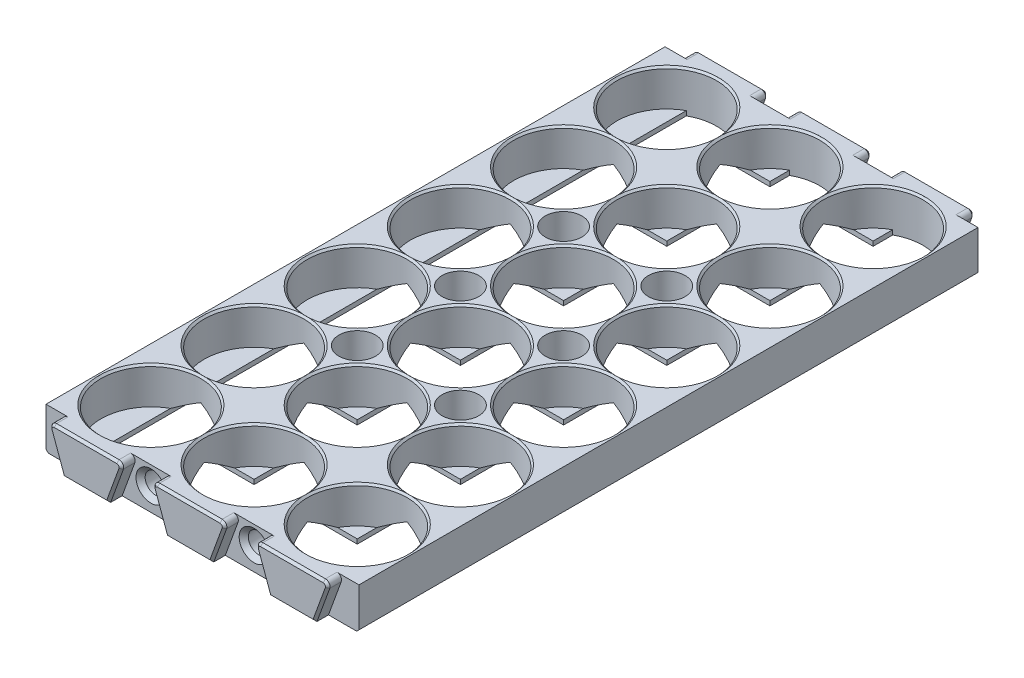
SolidWorks part; units mm, degrees
ref_plane "Front Plane" through (0, 0, 0) normal (0, 0, 1) x (1, 0, 0)
ref_plane "Top Plane" through (0, 0, 0) normal (0, 1, 0) x (1, 0, 0)
ref_plane "Right Plane" through (0, 0, 0) normal (1, 0, 0) x (0, 0, -1)
sketch "Sketch1" plane through (0, 0, 0) normal (0, 1, 0) x (1, 0, 0)
  line L0 (-11.25, 10.875) -> (11.25, 10.875) construction
  line L1 (-11.25, -11.25) -> (11.25, -11.25)
  line L2 (-11.25, -11.25) -> (-11.25, 11.25)
  line L3 (-11.25, 11.25) -> (11.25, 11.25)
  line L4 (11.25, -11.25) -> (11.25, 11.25)
  line L5 (-11.25, -11.25) -> (11.25, 11.25) construction
  line L6 (-11.25, 11.25) -> (11.25, -11.25) construction
  circle A0 centre (0, 0) radius 10.875
  point P0 (0, 0)
  dimension "D1" = 21.75
  dimension "D2" = 22.5
  dimension "D3" = 0.375
extrude "Boss-Extrude1" add sketch "Sketch1" along normal blind 8
sketch "Sketch2" plane through (0, 0, 0) normal (0, -1, 0) x (1, 0, 0)
  line L0 (5.25, 11.25) -> (-5.25, 11.25) construction
  line L1 (11.25, 11.25) -> (5.25, 11.25)
  line L2 (11.25, 11.25) -> (11.25, 5.25)
  line L3 (11.25, 5.25) -> (5.25, 5.25)
  line L4 (5.25, 11.25) -> (5.25, 5.25)
  line L5 (11.25, -11.25) -> (5.25, -11.25)
  line L6 (11.25, -11.25) -> (11.25, -5.25)
  line L7 (11.25, -5.25) -> (5.25, -5.25)
  line L8 (5.25, -11.25) -> (5.25, -5.25)
  line L9 (-11.25, -11.25) -> (-5.25, -11.25)
  line L10 (-11.25, -11.25) -> (-11.25, -5.25)
  line L11 (-11.25, -5.25) -> (-5.25, -5.25)
  line L12 (-5.25, -11.25) -> (-5.25, -5.25)
  line L13 (-11.25, 11.25) -> (-5.25, 11.25)
  line L14 (-11.25, 11.25) -> (-11.25, 5.25)
  line L15 (-11.25, 5.25) -> (-5.25, 5.25)
  line L16 (-5.25, 11.25) -> (-5.25, 5.25)
  line L17 (11.25, 5.25) -> (11.25, -5.25) construction
  line L18 (5.25, -11.25) -> (-5.25, -11.25) construction
  line L19 (-11.25, 5.25) -> (-11.25, -5.25) construction
  dimension "D1" = 10.5
extrude "Boss-Extrude2" add sketch "Sketch2" along normal blind 1
chamfer "Chamfer2" distance 0.4 angle 45 1 edges at (0, 8, 10.875)
pattern_linear "LPattern1" count 6 spacing 22.5 along (0, 0, 1) count 3 spacing 22.5 along (1, 0, 0) of "Boss-Extrude2", "Boss-Extrude1", "Chamfer2"
sketch "Sketch5" plane through (0, 0, -5.25) normal (0, 0, 1) x (1, 0, 0)
  line L25 (-5.25, -1) -> (-5.25, 0) construction
  line L26 (-5.25, -1) -> (-11.25, -1) construction
  line L27 (-11.25, -1) -> (-11.25, 0) construction
  line L29 (-5.25, 0) -> (-9.5238, 0) construction
  line L35 (-5.25, -1) -> (-5.25, 0)
  line L36 (-5.25, -1) -> (-11.25, -1)
  line L37 (-11.25, -1) -> (-11.25, 0)
  line L39 (-5.25, 0) -> (-11.25, 0)
  line L55 (56.25, -1) -> (50.25, -1)
  line L56 (56.25, -1) -> (56.25, 0)
  line L57 (56.25, 0) -> (50.25, 0)
  line L58 (50.25, -1) -> (50.25, 0)
  dimension "D1" = 6
extrude "Boss-Extrude3" add sketch "Sketch5" along normal up to surface (129 mm away)
sketch "Sketch6" plane through (0, 0, 0) normal (0, -1, 0) x (1, 0, 0)
  line L27 (39.75, -11.25) -> (50.25, -11.25) construction
  line L28 (50.25, -11.25) -> (50.25, -9.5238) construction
  line L29 (39.75, -9.5238) -> (39.75, -11.25) construction
  line L30 (17.25, -9.5238) -> (17.25, -11.25) construction
  line L31 (17.25, -11.25) -> (27.75, -11.25) construction
  line L32 (27.75, -11.25) -> (27.75, -9.5238) construction
  line L33 (-5.25, -9.5238) -> (-5.25, -11.25) construction
  line L34 (-5.25, -11.25) -> (5.25, -11.25) construction
  line L35 (5.25, -11.25) -> (5.25, -9.5238) construction
  line L51 (39.75, -11.25) -> (50.25, -11.25)
  line L52 (50.25, -11.25) -> (50.25, -9.5238)
  line L53 (39.75, -9.5238) -> (39.75, -11.25)
  line L54 (17.25, -9.5238) -> (17.25, -11.25)
  line L55 (17.25, -11.25) -> (27.75, -11.25)
  line L56 (27.75, -11.25) -> (27.75, -9.5238)
  line L57 (-5.25, -9.5238) -> (-5.25, -11.25)
  line L58 (-5.25, -11.25) -> (5.25, -11.25)
  line L59 (5.25, -11.25) -> (5.25, -9.5238)
  line L63 (50.25, 122.0238) -> (50.25, 123.75) construction
  line L64 (50.25, 123.75) -> (39.75, 123.75) construction
  line L65 (39.75, 123.75) -> (39.75, 122.0238) construction
  line L66 (27.75, 122.0238) -> (27.75, 123.75) construction
  line L67 (27.75, 123.75) -> (17.25, 123.75) construction
  line L68 (17.25, 123.75) -> (17.25, 122.0238) construction
  line L69 (5.25, 123.75) -> (-5.25, 123.75) construction
  line L70 (-5.25, 123.75) -> (-5.25, 122.0238) construction
  line L71 (5.25, 122.0238) -> (5.25, 123.75) construction
  line L75 (50.25, 122.0238) -> (50.25, 123.75)
  line L76 (50.25, 123.75) -> (39.75, 123.75)
  line L77 (39.75, 123.75) -> (39.75, 122.0238)
  line L78 (27.75, 122.0238) -> (27.75, 123.75)
  line L79 (27.75, 123.75) -> (17.25, 123.75)
  line L80 (17.25, 123.75) -> (17.25, 122.0238)
  line L81 (5.25, 123.75) -> (-5.25, 123.75)
  line L82 (-5.25, 123.75) -> (-5.25, 122.0238)
  line L83 (5.25, 122.0238) -> (5.25, 123.75)
  arc A9 (39.75, -9.5238) -> (50.25, -9.5238) centre (45, 0) ccw construction
  arc A10 (17.25, -9.5238) -> (27.75, -9.5238) centre (22.5, 0) ccw construction
  arc A11 (-5.25, -9.5238) -> (5.25, -9.5238) centre (0, 0) ccw construction
  arc A17 (39.75, -9.5238) -> (50.25, -9.5238) centre (45, 0) ccw
  arc A18 (17.25, -9.5238) -> (27.75, -9.5238) centre (22.5, 0) ccw
  arc A19 (-5.25, -9.5238) -> (5.25, -9.5238) centre (0, 0) ccw
  arc A21 (50.25, 122.0238) -> (39.75, 122.0238) centre (45, 112.5) ccw construction
  arc A22 (27.75, 122.0238) -> (17.25, 122.0238) centre (22.5, 112.5) ccw construction
  arc A23 (5.25, 122.0238) -> (-5.25, 122.0238) centre (0, 112.5) ccw construction
  arc A25 (50.25, 122.0238) -> (39.75, 122.0238) centre (45, 112.5) ccw
  arc A26 (27.75, 122.0238) -> (17.25, 122.0238) centre (22.5, 112.5) ccw
  arc A27 (5.25, 122.0238) -> (-5.25, 122.0238) centre (0, 112.5) ccw
extrude "Boss-Extrude4" add sketch "Sketch6" along normal up to surface (1 mm away) up to face at (-8.25, -1, 56.25)
sketch "Sketch7" plane through (0, 0, 0) normal (0, 0, 1) x (1, 0, 0)
  line L1 (-5.25, 0) -> (5.25, 0)
  line L2 (-5.25, 0) -> (0, 5.25) construction
  line L3 (0, 5.25) -> (5.25, 0) construction
  line L4 (0, 0) -> (0, 7.975) construction
  line L6 (-5.25, 0) -> (0, 3.0311)
  line L7 (0, 3.0311) -> (5.25, 0)
  line L9 (-5.25, -1) -> (-5.25, 0) construction
  line L10 (5.25, -1) -> (5.25, 0) construction
  line L11 (-5.25, -1) -> (-5.25, 0) construction
  line L12 (5.25, -1) -> (5.25, 0) construction
  line L13 (17.25, 0) -> (22.5, 3.0311)
  line L14 (22.5, 3.0311) -> (27.75, 0)
  line L15 (17.25, 0) -> (27.75, 0)
  line L16 (39.75, 0) -> (45, 3.0311)
  line L17 (45, 3.0311) -> (50.25, 0)
  line L18 (39.75, 0) -> (50.25, 0)
  line L22 (-5.25, 0) -> (17.25, 0) construction
  line L23 (62.25, 0) -> (67.5, 3.0311) [skipped]
  line L24 (67.5, 3.0311) -> (72.75, 0) [skipped]
  line L25 (62.25, 0) -> (72.75, 0) [skipped]
  parabola Q0 (0.7504, 8) -> (-0.7504, 8) focus (0, 13.6125) apex (0, 7.975) construction
  dimension "D1" = 45
  dimension "D2" = 30
  dimension "D3" = 4.9439
  dimension "D5" = 22.5
  dimension "D4" = 4
extrude "Cut-Extrude1" cut sketch "Sketch7" along normal up to surface (117.75 mm away) up to face at (11.25, -0.3333, 117.75)
sketch "Sketch16" plane through (0, 0, 0) normal (1, 0, 0) x (0, 0, -1)
  line L2 (-5.25, -1) -> (-5.25, 0) construction
  line L3 (5.25, -1) -> (5.25, 0) construction
  line L4 (-5.25, 0) -> (0, 3.0311)
  line L5 (0, 3.0311) -> (5.25, 0)
  line L6 (-5.25, 0) -> (5.25, 0)
  line L7 (-5.25, -1) -> (-5.25, 0) construction
  line L8 (5.25, -1) -> (5.25, 0) construction
  line L9 (-22.5, 3.0311) -> (-17.25, 0)
  line L10 (-27.75, 0) -> (-17.25, 0)
  line L11 (-27.75, 0) -> (-22.5, 3.0311)
  line L12 (-45, 3.0311) -> (-39.75, 0)
  line L13 (-50.25, 0) -> (-39.75, 0)
  line L14 (-50.25, 0) -> (-45, 3.0311)
  line L15 (-67.5, 3.0311) -> (-62.25, 0)
  line L16 (-72.75, 0) -> (-62.25, 0)
  line L17 (-72.75, 0) -> (-67.5, 3.0311)
  line L18 (-90, 3.0311) -> (-84.75, 0)
  line L19 (-95.25, 0) -> (-84.75, 0)
  line L20 (-95.25, 0) -> (-90, 3.0311)
  line L21 (-112.5, 3.0311) -> (-107.25, 0)
  line L22 (-117.75, 0) -> (-107.25, 0)
  line L23 (-117.75, 0) -> (-112.5, 3.0311)
  line L42 (0, 3.0311) -> (-22.5, 3.0311) construction
  line L43 (-135, 3.0311) -> (-129.75, 0) [skipped]
  line L44 (-140.25, 0) -> (-129.75, 0) [skipped]
  line L45 (-140.25, 0) -> (-135, 3.0311) [skipped]
  line L46 (-157.5, 3.0311) -> (-152.25, 0) [skipped]
  line L47 (-162.75, 0) -> (-152.25, 0) [skipped]
  line L48 (-162.75, 0) -> (-157.5, 3.0311) [skipped]
  line L49 (-180, 3.0311) -> (-174.75, 0) [skipped]
  line L50 (-185.25, 0) -> (-174.75, 0) [skipped]
  line L51 (-185.25, 0) -> (-180, 3.0311) [skipped]
  line L52 (-202.5, 3.0311) -> (-197.25, 0) [skipped]
  line L53 (-207.75, 0) -> (-197.25, 0) [skipped]
  line L54 (-207.75, 0) -> (-202.5, 3.0311) [skipped]
  line L55 (-225, 3.0311) -> (-219.75, 0) [skipped]
  line L56 (-230.25, 0) -> (-219.75, 0) [skipped]
  line L57 (-230.25, 0) -> (-225, 3.0311) [skipped]
  line L58 (-247.5, 3.0311) -> (-242.25, 0) [skipped]
  line L59 (-252.75, 0) -> (-242.25, 0) [skipped]
  line L60 (-252.75, 0) -> (-247.5, 3.0311) [skipped]
  dimension "D1" = 30
  dimension "D3" = 22.5
  dimension "D2" = 12
extrude "Cut-Extrude7" cut sketch "Sketch16" along normal up to surface (39.75 mm away) up to face at (39.75, -0.3333, 11.25)
sketch "Sketch8" plane through (0, 0, -11.25) normal (0, 0, -1) x (-1, 0, 0)
  line L0 (0, -1) -> (0, 8) construction
  line L1 (-27.4743, -1) -> (-30.75, 8)
  line L2 (0.7504, 8) -> (11.25, 8) construction
  line L3 (4.9743, -1) -> (-4.9743, -1)
  line L4 (-4.9743, -1) -> (-8.25, 8)
  line L5 (-8.25, 8) -> (8.25, 8)
  line L6 (4.9743, -1) -> (8.25, 8)
  line L7 (11.25, 8) -> (11.25, -1) construction
  line L8 (11.25, -1) -> (-56.25, -1) construction
  line L9 (-30.75, 8) -> (-14.25, 8)
  line L10 (0.7504, 8) -> (11.25, 8) construction
  line L11 (-17.5257, -1) -> (-14.25, 8)
  line L12 (-17.5257, -1) -> (-27.4743, -1)
  line L13 (-49.9743, -1) -> (-53.25, 8)
  line L14 (-53.25, 8) -> (-36.75, 8)
  line L15 (-40.0257, -1) -> (-36.75, 8)
  line L16 (-40.0257, -1) -> (-49.9743, -1)
  line L21 (-4.9743, -1) -> (-27.4743, -1) construction
  line L22 (0.7504, 8) -> (11.25, 8) construction
  line L23 (-72.4743, -1) -> (-75.75, 8) [skipped]
  line L24 (-75.75, 8) -> (-59.25, 8) [skipped]
  line L25 (-62.5257, -1) -> (-59.25, 8) [skipped]
  line L26 (-62.5257, -1) -> (-72.4743, -1) [skipped]
  dimension "D1" = 70
  dimension "D2" = 3
  dimension "D4" = 22.5
  dimension "D5" = 9
  dimension "D3" = 4
sketch "Sketch9" plane through (0, 0, 123.75) normal (0, 0, 1) x (1, 0, 0)
  line L24 (-4.9743, -1) -> (4.9743, -1)
  line L25 (4.9743, -1) -> (8.25, 8)
  line L26 (8.25, 8) -> (-8.25, 8)
  line L27 (-8.25, 8) -> (-4.9743, -1)
  line L28 (-4.9743, -1) -> (4.9743, -1)
  line L29 (4.9743, -1) -> (8.25, 8)
  line L30 (8.25, 8) -> (-8.25, 8)
  line L31 (-8.25, 8) -> (-4.9743, -1)
  line L40 (49.9743, -1) -> (53.25, 8)
  line L41 (53.25, 8) -> (36.75, 8)
  line L42 (36.75, 8) -> (40.0257, -1)
  line L43 (40.0257, -1) -> (49.9743, -1)
  line L44 (49.9743, -1) -> (53.25, 8)
  line L45 (53.25, 8) -> (36.75, 8)
  line L46 (36.75, 8) -> (40.0257, -1)
  line L47 (40.0257, -1) -> (49.9743, -1)
  line L48 (14.25, 8) -> (17.5257, -1)
  line L49 (17.5257, -1) -> (27.4743, -1)
  line L50 (27.4743, -1) -> (30.75, 8)
  line L51 (30.75, 8) -> (14.25, 8)
  line L52 (14.25, 8) -> (17.5257, -1)
  line L53 (17.5257, -1) -> (27.4743, -1)
  line L54 (27.4743, -1) -> (30.75, 8)
  line L55 (30.75, 8) -> (14.25, 8)
  dimension "D1" = 0
  dimension "D3" = 0
  dimension "D4" = 0
extrude "Boss-Extrude5" add sketch "Sketch8" along normal blind 3
extrude "Boss-Extrude6" add sketch "Sketch9" along normal blind 3
fillet "Fillet1" radius 1 12 edges at (8.25, 8, 125.25) (14.25, 8, 125.25) (30.75, 8, 125.25) (36.75, 8, 125.25) (53.25, 8, 125.25) (-8.25, 8, 125.25) (53.25, 8, -12.75) (30.75, 8, -12.75) (36.75, 8, -12.75) (8.25, 8, -12.75) (14.25, 8, -12.75) (-8.25, 8, -12.75)
chamfer "Chamfer3" distance 0.5 angle 45 36 edges at (6.3679, 2.829, -14.25) (0, 8, -14.25) (-6.3679, 2.829, -14.25) (51.3679, 2.829, -14.25) (45, 8, -14.25) (38.6321, 2.829, -14.25) (28.8679, 2.829, -14.25) (22.5, 8, -14.25) (16.1321, 2.829, -14.25) (51.3679, 2.829, 126.75) (38.6321, 2.829, 126.75) (45, 8, 126.75) (28.8679, 2.829, 126.75) (16.1321, 2.829, 126.75) (22.5, 8, 126.75) (6.3679, 2.829, 126.75) (-6.3679, 2.829, 126.75) (0, 8, 126.75) (45, -1, 126.75) (22.5, -1, 126.75) (0, -1, 126.75) (45, -1, -14.25) (22.5, -1, -14.25) (0, -1, -14.25) (52.641, 7.5736, 126.75) (37.359, 7.5736, 126.75) (30.141, 7.5736, 126.75) (14.859, 7.5736, 126.75) (7.641, 7.5736, 126.75) (-7.641, 7.5736, 126.75) (52.641, 7.5736, -14.25) (37.359, 7.5736, -14.25) (30.141, 7.5736, -14.25) (14.859, 7.5736, -14.25) (7.641, 7.5736, -14.25) (-7.641, 7.5736, -14.25)
sketch "Sketch10" plane through (0, 0, -11.25) normal (0, 0, -1) x (-1, 0, 0)
  line L0 (-11.25, -1) -> (-11.25, 8) construction
  line L1 (-29.3219, 8) -> (-15.6781, 8) construction
  line L2 (-4.9743, -1) -> (-17.5257, -1) construction
  line L3 (-26.9422, -1) -> (-18.0578, -1) construction
  line L4 (-14.25, 8) -> (-8.25, 8) construction
  line L5 (-22.5, 8) -> (-22.5, -1) construction
  circle A0 centre (-11.25, 4) radius 2.25
  circle A1 centre (-33.75, 4) radius 2.25
  dimension "D2" = 4.5
  dimension "D1" = 4
sketch "Sketch11" plane through (0, 0, 123.75) normal (0, 0, 1) x (1, 0, 0)
  circle A0 centre (11.25, 4) radius 2.25 construction
  circle A1 centre (11.25, 4) radius 2.25
  circle A2 centre (33.75, 4) radius 2.25 construction
  circle A3 centre (33.75, 4) radius 2.25
extrude "Cut-Extrude2" cut sketch "Sketch10" against normal blind 5
extrude "Cut-Extrude3" cut sketch "Sketch11" against normal blind 5
chamfer "Chamfer5" distance 1 angle 45 4 edges at (36, 4, -11.25) (9, 4, -11.25) (13.5, 4, 123.75) (36, 4, 123.75)
sketch "Sketch17" plane through (0, -1, 0) normal (0, -1, 0) x (1, 0, 0)
  line L0 (5.25, 5.25) -> (17.25, 17.25) construction
  line L1 (11.25, 11.25) -> (33.75, 11.25) construction
  line L2 (11.25, 11.25) -> (11.25, 33.75) construction
  line L3 (-11.25, 56.25) -> (56.25, 56.25) construction
  line L4 (-11.25, 123.75) -> (-11.25, -11.25) construction
  line L5 (56.25, -11.25) -> (56.25, 123.75) construction
  circle A0 centre (11.25, 11.25) radius 4 construction
  circle A1 centre (33.75, 11.25) radius 4 construction
  circle A3 centre (33.75, 33.75) radius 4
  circle A5 centre (33.75, 56.25) radius 4
  circle A7 centre (33.75, 78.75) radius 4
  circle A9 centre (33.75, 101.25) radius 4 construction
  circle A23 centre (11.25, 33.75) radius 4
  circle A24 centre (11.25, 56.25) radius 4
  circle A25 centre (11.25, 78.75) radius 4
  circle A26 centre (11.25, 101.25) radius 4 construction
  circle A33 centre (33.75, 146.25) radius 4 [skipped]
  circle A35 centre (33.75, 168.75) radius 4 [skipped]
  circle A36 centre (33.75, 191.25) radius 4 [skipped]
  circle A38 centre (33.75, 213.75) radius 4 [skipped]
  circle A40 centre (33.75, 236.25) radius 4 [skipped]
  circle A42 centre (11.25, 146.25) radius 4 [skipped]
  circle A43 centre (11.25, 191.25) radius 4 [skipped]
  circle A44 centre (11.25, 213.75) radius 4 [skipped]
  circle A45 centre (11.25, 236.25) radius 4 [skipped]
  circle A47 centre (11.25, 168.75) radius 4 construction
  circle A48 centre (33.75, 123.75) radius 4 [skipped]
  circle A50 centre (11.25, 123.75) radius 4 [skipped]
  dimension "D5" = 22.5
  dimension "D4" = 22.5
  dimension "D1" = 8
  dimension "D6" = 45
  dimension "D3" = 11
extrude "Cut-Extrude8" cut sketch "Sketch17" against normal through all
sketch "Sketch18" plane through (0, -1, 0) normal (0, -1, 0) x (1, 0, 0)
  line L0 (39.75, 5.25) -> (39.75, 17.25) construction
  line L34 (27.75, 17.25) -> (39.75, 5.25) construction
  line L35 (5.25, 17.25) -> (17.25, 5.25) construction
  line L36 (17.25, 5.25) -> (17.25, 17.25) construction
  line L37 (5.25, 5.25) -> (17.25, 5.25) construction
  line L38 (63.9319, 56.25) -> (-11.25, 56.25) construction
  line L40 (-11.25, 123.75) -> (-11.25, -11.25) construction
  line L41 (5.25, 95.25) -> (17.25, 107.25) construction
  line L42 (27.75, 95.25) -> (39.75, 107.25) construction
  circle A0 centre (11.25, 11.25) radius 2.1
  circle A1 centre (33.75, 11.25) radius 2.1
  circle A5 centre (33.75, 101.25) radius 2.1
  circle A6 centre (11.25, 101.25) radius 2.1
  dimension "D1" = 4.2
extrude "Cut-Extrude9" cut sketch "Sketch18" against normal blind 4
sketch "Sketch19" plane through (0, -1, 0) normal (0, -1, 0) x (1, 0, 0)
  line L0 (56.25, 56.25) -> (-11.25, 56.25) construction
  line L2 (-11.25, 123.75) -> (-11.25, -11.25) construction
  line L3 (56.25, -11.25) -> (56.25, 123.75) construction
  circle A2 centre (33.75, 11.25) radius 1.7
  circle A3 centre (11.25, 11.25) radius 1.7
  circle A4 centre (11.25, 101.25) radius 1.7
  circle A5 centre (33.75, 101.25) radius 1.7
  dimension "D1" = 3.4
  dimension "D2" = 22.5
extrude "Cut-Extrude10" cut sketch "Sketch19" against normal offset from surface (7 mm away) 2 up to face at (22.5, 8, -10.6182)
chamfer "Chamfer6" distance 1 angle 45 4 edges at (11.25, -1, 103.35) (11.25, -1, 9.15) (33.75, -1, 9.15) (33.75, -1, 103.35)
sketch "Sketch22" plane through (0, 8, 0) normal (0, 1, 0) x (1, 0, 0)
  line L0 (15.6781, 14.25) -> (29.3219, 14.25) construction
  line L1 (-11.25, 11.25) -> (-11.625, 11.25)
  line L2 (-11.25, 11.25) -> (-11.25, -123.75)
  line L3 (-11.25, -123.75) -> (-11.625, -123.75)
  line L4 (-11.625, 11.25) -> (-11.625, -123.75)
  line L5 (22.5, 14.25) -> (22.5, -126.75) construction
  line L7 (29.3219, -126.75) -> (15.6781, -126.75) construction
  line L13 (-4.9743, -123.75) -> (-11.25, -123.75) construction
  line L14 (56.625, 11.25) -> (56.625, -123.75)
  line L15 (56.25, -123.75) -> (56.625, -123.75)
  line L16 (56.25, 11.25) -> (56.25, -123.75)
  line L17 (56.25, 11.25) -> (56.625, 11.25)
  arc A1 (-5.25, 9.5238) -> (-5.25, -9.5238) centre (0, 0) ccw construction
  point P10 (-10.875, 0)
  dimension "D1" = 0.75
  dimension "D2" = 0.375
  dimension "D3" = 34.125
extrude "Boss-Extrude7" add sketch "Sketch22" against normal up to surface (9 mm away)
sketch "Sketch14" plane through (0, -1, 0) normal (0, -1, 0) x (1, 0, 0)
  line L0 (-5.25, 56.25) -> (-11.625, 56.25) construction
  line L2 (-10.25, 53.7941) -> (-10.25, 58.7059)
  line L3 (-5.25, 56.25) -> (50.25, 56.25) construction
  line L4 (-11.625, -11.25) -> (-11.625, 123.75) construction
  line L30 (50.25, 122.0238) -> (50.25, -9.5238) construction
  line L39 (22.5, 56.25) -> (22.5, -14.25) construction
  line L40 (26.9422, -14.25) -> (18.0578, -14.25) construction
  line L53 (-5.25, 11.25) -> (-11.625, 11.25) construction
  line L54 (-5.25, 9.5238) -> (-5.25, 12.9762) construction
  line L56 (-6.25, 55.25) -> (-6.25, 57.25)
  line L57 (-10.25, 13.7059) -> (-6.25, 12.25)
  line L58 (-5.25, -9.5238) -> (-5.25, 122.0238) construction
  line L59 (50.25, 11.25) -> (56.625, 11.25) construction
  line L60 (50.25, 56.25) -> (56.625, 56.25) construction
  line L61 (55.25, 53.7941) -> (51.25, 55.25)
  line L62 (55.25, 8.7941) -> (51.25, 10.25)
  line L64 (51.25, 10.25) -> (51.25, 12.25)
  line L65 (55.25, 8.7941) -> (55.25, 13.7059)
  line L66 (55.25, 13.7059) -> (51.25, 12.25)
  line L67 (51.25, 55.25) -> (51.25, 57.25)
  line L69 (55.25, 53.7941) -> (55.25, 58.7059)
  line L70 (50.25, 101.25) -> (56.625, 101.25) construction
  line L71 (-5.25, 101.25) -> (-11.625, 101.25) construction
  line L72 (-10.25, 8.7941) -> (-10.25, 13.7059)
  line L74 (-6.25, 10.25) -> (-6.25, 12.25)
  line L75 (-10.25, 8.7941) -> (-6.25, 10.25)
  line L76 (-10.25, 58.7059) -> (-6.25, 57.25)
  line L77 (-10.25, 103.7059) -> (-6.25, 102.25)
  line L78 (-6.25, 102.25) -> (-6.25, 100.25)
  line L79 (-10.25, 103.7059) -> (-10.25, 98.7941)
  line L84 (55.25, 98.7941) -> (51.25, 100.25)
  line L85 (55.25, 103.7059) -> (55.25, 98.7941)
  line L86 (51.25, 102.25) -> (51.25, 100.25)
  line L87 (55.25, 103.7059) -> (51.25, 102.25)
  line L93 (55.25, 58.7059) -> (51.25, 57.25)
  line L94 (-10.25, 98.7941) -> (-6.25, 100.25)
  line L98 (-10.25, 53.7941) -> (-6.25, 55.25)
  point P14 (-10.25, 56.25)
  point P18 (-6.25, 11.25)
  point P21 (-10.25, 11.25)
  point P36 (55.25, 11.25)
  point P37 (51.25, 11.25)
  point P51 (55.25, 56.25)
  point P52 (51.25, 56.25)
  point P56 (-6.25, 56.25)
  point P57 (51.25, 101.25)
  point P58 (55.25, 101.25)
  point P59 (-10.25, 101.25)
  point P60 (-6.25, 101.25)
  dimension "D1" = 1.375
  dimension "D2" = 70
  dimension "D3" = 4
  dimension "D4" = 1
  dimension "D6" = 4
  dimension "D7" = 70
  dimension "D8" = 1
extrude "Cut-Extrude11" cut sketch "Sketch14" against normal blind 2
chamfer "Chamfer7" distance 0.5 angle 45 24 edges at (-6.25, -1, 101.25) (-8.25, -1, 99.5221) (-10.25, -1, 101.25) (-8.25, -1, 102.9779) (51.25, -1, 101.25) (53.25, -1, 99.5221) (55.25, -1, 101.25) (53.25, -1, 102.9779) (55.25, -1, 56.25) (53.25, -1, 57.9779) (51.25, -1, 56.25) (53.25, -1, 54.5221) (-10.25, -1, 56.25) (-8.25, -1, 57.9779) (-6.25, -1, 56.25) (-8.25, -1, 54.5221) (51.25, -1, 11.25) (53.25, -1, 9.5221) (55.25, -1, 11.25) (53.25, -1, 12.9779) (-6.25, -1, 11.25) (-8.25, -1, 9.5221) (-10.25, -1, 11.25) (-8.25, -1, 12.9779)
chamfer "Chamfer9" distance 0.5 angle 45 2 edges at (-11.625, -1, 56.25) (56.625, -1, 56.25)
equation "\"cell_side\"= 22.50"
equation "\"D2@Sketch1\"=\"cell_side\""
equation "\"D5@Sketch7\"=\"cell_side\""
equation "\"D3@Sketch16\"=\"cell_side\""
equation "\"D4@Sketch8\"=\"cell_side\""
equation "\"D5@Sketch17\"=\"cell_side\""
equation "\"D3@LPattern1\"=\"cell_side\""
equation "\"D4@LPattern1\"=\"cell_side\""
equation "\"D4@Sketch17\"=\"cell_side\""
